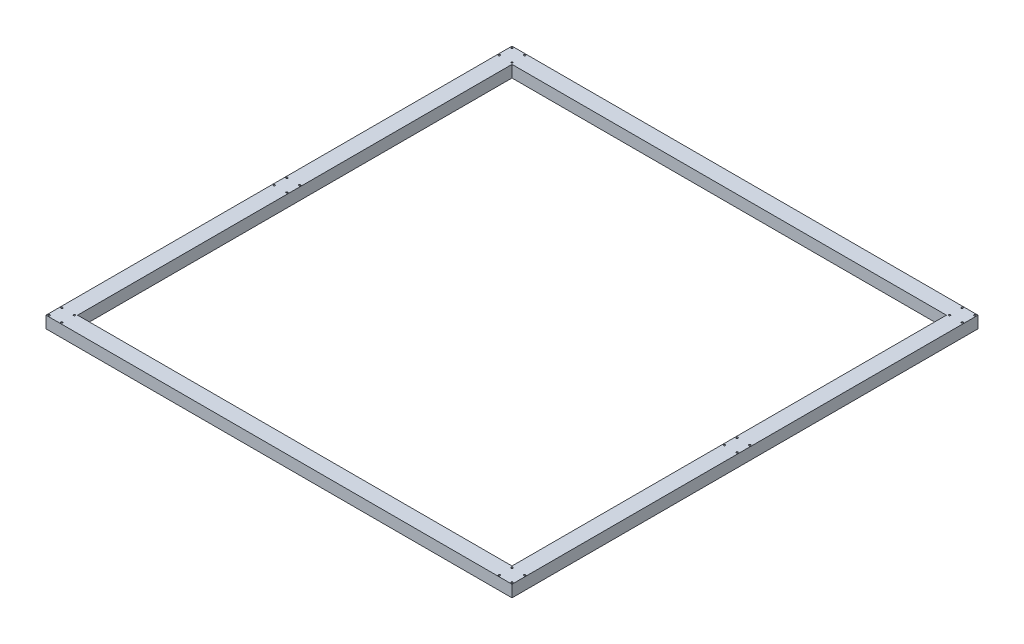
SolidWorks part; units mm, degrees
material "Concreto"
ref_plane "Plano frontal" through (0, 0, 0) normal (0, 0, 1) x (1, 0, 0)
ref_plane "Plano superior" through (0, 0, 0) normal (0, 1, 0) x (1, 0, 0)
ref_plane "Plano direito" through (0, 0, 0) normal (1, 0, 0) x (0, 0, -1)
sketch "Esboço1" plane through (0, 0, 0) normal (0, 1, 0) x (1, 0, 0)
  line L5 (-2750, 2750) -> (2750, 2750)
  line L6 (-2750, 2750) -> (-2750, -2750)
  line L11 (-2750, -2750) -> (2750, -2750)
  line L12 (2750, 2750) -> (2750, -2750)
  line L13 (-2750, 2750) -> (2750, -2750) construction
  line L14 (-2750, -2750) -> (2750, 2750) construction
  line L15 (-2950, 2950) -> (2950, 2950)
  line L16 (-2950, 2950) -> (-2950, -2950)
  line L17 (-2950, -2950) -> (2950, -2950)
  line L18 (2950, 2950) -> (2950, -2950)
  line L19 (-2950, 2950) -> (2950, -2950) construction
  line L20 (-2950, -2950) -> (2950, 2950) construction
  point P0 (0, 0)
  point P6 (0, 0)
  dimension "D1" = 5500
  dimension "D2" = 5500
  dimension "D3" = 200
  dimension "D4" = 200
extrude "Ressalto-extrusão1" add sketch "Esboço1" along normal blind 150
sketch "Esboço2" plane through (0, 150, 0) normal (0, 1, 0) x (1, 0, 0)
  line L0 (-2950, 0) -> (2950, 0) construction
  line L1 (-2950, 2950) -> (-2950, -2950) construction
  line L2 (2950, -2950) -> (2950, 2950) construction
  line L3 (0, 2950) -> (0, -2950) construction
  line L4 (2950, 2950) -> (-2950, 2950) construction
  line L5 (-2950, -2950) -> (2950, -2950) construction
  line L6 (-2950, 2950) -> (-2750, 2750) construction
  line L7 (2950, 2950) -> (2750, 2750) construction
  line L8 (2950, -2950) -> (2750, -2750) construction
  line L9 (-2950, -2950) -> (-2750, -2750) construction
  line L10 (-2850, 2850) -> (2850, 2850) construction
  line L11 (-2750, 2750) -> (-2750, 0) construction
  line L12 (-2850, -2850) -> (2850, -2850) construction
  line L13 (-2750, 2750) -> (-2750, -2750) construction
  line L14 (-2750, 0) -> (-2750, -2750) construction
  line L15 (2750, 2750) -> (2750, 0) construction
  line L16 (2750, -2750) -> (2750, 2750) construction
  line L17 (2750, 0) -> (2750, -2750) construction
  line L18 (-2750, 2750) -> (0, 2750) construction
  line L19 (2750, 2750) -> (-2750, 2750) construction
  line L20 (0, 2750) -> (2750, 2750) construction
  point P32 (-2750, -1375)
  point P36 (-2750, 1375)
  point P40 (2750, -1375)
  point P41 (2750, 1375)
  point P42 (1375, 2750)
  point P46 (-1375, 2750)
ref_plane "Plano1" through (0, 0, -2850) normal (0, 0, 1) x (1, 0, 0)
sketch "Esboço4" plane through (0, 0, -2850) normal (0, 0, 1) x (1, 0, 0)
  line L0 (-2850, 150) -> (2850, 150) construction
  line L1 (-2850, 150) -> (2850, 150) construction
  line L2 (2850, 150) -> (2850, 2850) construction
  line L3 (-2850, 150) -> (-2850, 3250) construction
  line L4 (2850, 2850) -> (-2850, 2850) construction
  line L6 (-2850, 3250) -> (2850, 2850) construction
  line L7 (0, 3050) -> (-14.0351, 2850) construction
  line L8 (2850, 2250) -> (-2850, 2250) construction
  line L9 (2850, 2250) -> (2250, 2850) construction
  line L10 (-2850, 2250) -> (-1915.5738, 3184.4262) construction
  dimension "D1" = 2700
  dimension "D2" = 3100
  dimension "D3" = 2100
  dimension "D4" = 45
  dimension "D5" = 45
ref_plane "Plano2" through (0, 75, 0) normal (0, 1, 0) x (1, 0, 0)
sketch "Esboço5" plane through (0, 150, 0) normal (0, 1, 0) x (1, 0, 0)
  line L0 (0, -2775.9324) -> (0, 2775.9324) construction
  circle A1 centre (-2930, 2930) radius 11 construction
  circle A2 centre (-2930, 2930) radius 11
  circle A3 centre (-2770, 2930) radius 11
  circle A4 centre (-2770, 2770) radius 11
  circle A5 centre (-2930, 2770) radius 11
  circle A6 centre (-2930, 80) radius 11 construction
  circle A7 centre (-2930, 80) radius 11
  circle A8 centre (-2770, 80) radius 11
  circle A9 centre (-2770, -80) radius 11
  circle A10 centre (-2930, -80) radius 11
  circle A11 centre (-2930, -2770) radius 11 construction
  circle A12 centre (-2930, -2770) radius 11
  circle A13 centre (-2770, -2770) radius 11
  circle A14 centre (-2770, -2930) radius 11
  circle A15 centre (-2930, -2930) radius 11
  circle A16 centre (2770, -2930) radius 11
  circle A17 centre (2930, -2930) radius 11
  circle A18 centre (2770, -2770) radius 11
  circle A19 centre (2930, -2770) radius 11
  circle A20 centre (2770, 2770) radius 11
  circle A21 centre (2930, 2770) radius 11
  circle A22 centre (2770, 2930) radius 11
  circle A23 centre (2930, 2930) radius 11
  circle A24 centre (2770, -80) radius 11
  circle A25 centre (2930, -80) radius 11
  circle A26 centre (2770, 80) radius 11
  circle A27 centre (2930, 80) radius 11
  dimension "D1" = 2
  dimension "D2" = 2
  dimension "D3" = 2
  dimension "D4" = 2
  dimension "D5" = 2
  dimension "D6" = 2
extrude "Corte-extrusão1" cut sketch "Esboço5" against normal up to surface (150 mm away) up to face at (0, 0, 0)
